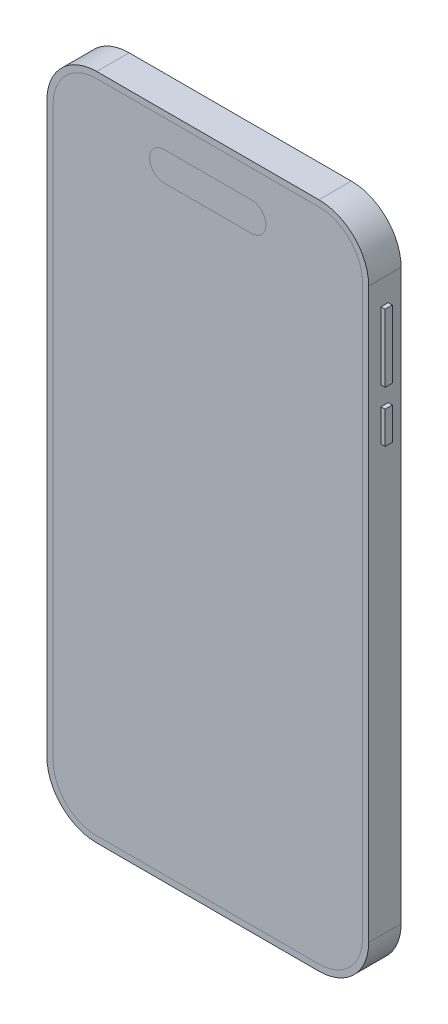
SolidWorks part; units mm, degrees
ref_plane "前视基准面" through (0, 0, 0) normal (0, 0, 1) x (1, 0, 0)
ref_plane "上视基准面" through (0, 0, 0) normal (0, 1, 0) x (1, 0, 0)
ref_plane "右视基准面" through (0, 0, 0) normal (1, 0, 0) x (0, 0, -1)
other "Configuration Table"
sketch "草图1" plane through (0, 0, 0) normal (0, 0, 1) x (1, 0, 0)
  line L1 (-26.75, -80.45) -> (26.75, -80.45)
  line L2 (-38.75, -68.45) -> (-38.75, 68.45)
  line L3 (-26.75, 80.45) -> (26.75, 80.45)
  line L4 (38.75, -68.45) -> (38.75, 68.45)
  line L5 (-38.75, -80.45) -> (38.75, 80.45) construction
  line L6 (-38.75, 80.45) -> (38.75, -80.45) construction
  arc A0 (26.75, -80.45) -> (38.75, -68.45) centre (26.75, -68.45) ccw
  arc A1 (-38.75, 68.45) -> (-26.75, 80.45) centre (-26.75, 68.45) cw
  arc A2 (-26.75, -80.45) -> (-38.75, -68.45) centre (-26.75, -68.45) cw
  arc A3 (26.75, 80.45) -> (38.75, 68.45) centre (26.75, 68.45) cw
  point P0 (0, 0)
  dimension "D3" = 12
  dimension "D1" = 77.5
  dimension "D2" = 160.9
extrude "凸台-拉伸1" add sketch "草图1" along normal blind 7.8
sketch "草图4" plane through (0, 0, 7.8) normal (0, 0, 1) x (1, 0, 0)
  line L0 (-10.5, 68.8) -> (10.5, 68.8) construction
  line L1 (-10.5, 72.3) -> (10.5, 72.3)
  line L2 (-10.5, 65.3) -> (10.5, 65.3)
  line L3 (26.75, 80.45) -> (-26.75, 80.45) construction
  arc A0 (-10.5, 72.3) -> (-10.5, 65.3) centre (-10.5, 68.8) ccw
  arc A1 (10.5, 65.3) -> (10.5, 72.3) centre (10.5, 68.8) ccw
  point P2 (0, 68.8)
  dimension "D1" = 3.5
  dimension "D2" = 21
  dimension "D3" = 8.15
split line "分割线1"
sketch "草图7" plane through (0, 0, 7.8) normal (0, 0, 1) x (1, 0, 0)
sketch "草图9" plane through (0, 0, 7.8) normal (0, 0, 1) x (1, 0, 0)
sketch "草图10" plane through (0, 0, 7.8) normal (0, 0, 1) x (1, 0, 0)
  line L2 (-37.25, 68.45) -> (-37.25, -68.45)
  line L3 (-37.25, 68.45) -> (-37.25, -68.45)
  line L5 (26.75, 78.95) -> (-26.75, 78.95)
  line L6 (26.75, 78.95) -> (-26.75, 78.95)
  line L8 (37.25, -68.45) -> (37.25, 68.45)
  line L9 (37.25, -68.45) -> (37.25, 68.45)
  line L11 (-26.75, -78.95) -> (26.75, -78.95)
  line L12 (-26.75, -78.95) -> (26.75, -78.95)
  arc A2 (-26.75, 78.95) -> (-37.25, 68.45) centre (-26.75, 68.45) ccw
  arc A3 (-26.75, 78.95) -> (-37.25, 68.45) centre (-26.75, 68.45) ccw
  arc A5 (37.25, 68.45) -> (26.75, 78.95) centre (26.75, 68.45) ccw
  arc A6 (37.25, 68.45) -> (26.75, 78.95) centre (26.75, 68.45) ccw
  arc A7 (-37.25, -68.45) -> (-26.75, -78.95) centre (-26.75, -68.45) ccw
  arc A8 (26.75, -78.95) -> (37.25, -68.45) centre (26.75, -68.45) ccw
  arc A9 (26.75, -78.95) -> (37.25, -68.45) centre (26.75, -68.45) ccw
  arc A10 (-37.25, -68.45) -> (-26.75, -78.95) centre (-26.75, -68.45) ccw
  dimension "D1" = 1.5
  dimension "D2" = 1.5
  dimension "D3" = 1.5
  dimension "D4" = 1.5
  dimension "D5" = 1.5
  dimension "D6" = 1.5
  dimension "D7" = 1.5
  dimension "D8" = 1.5
split line "分割线3"
sketch "草图15" plane through (0, 0, 0) normal (0, 0, -1) x (-1, 0, 0)
  line L0 (-38.75, -68.45) -> (-38.75, 68.45) construction
  line L1 (-27.75, 37.45) -> (-5.75, 37.45)
  line L2 (-35.75, 45.45) -> (-35.75, 67.45)
  line L3 (-27.75, 75.45) -> (-5.75, 75.45)
  line L4 (2.25, 45.45) -> (2.25, 67.45)
  line L5 (-16.75, 75.45) -> (-16.75, 37.45) construction
  line L6 (-35.75, 56.45) -> (2.25, 56.45) construction
  line L7 (-26.75, 80.45) -> (26.75, 80.45) construction
  line L8 (-24.5442, 65.45) -> (-24.5442, 47.45) construction
  line L9 (-24.5442, 47.45) -> (-8.9558, 56.45) construction
  line L10 (-8.9558, 56.45) -> (-24.5442, 65.45) construction
  line L11 (-24.5442, 56.45) -> (-8.9558, 56.45)
  circle A0 centre (-24.5442, 65.45) radius 7.5
  circle A1 centre (-8.9558, 56.45) radius 7.5
  circle A2 centre (-24.5442, 47.45) radius 7.5
  arc A3 (-5.75, 75.45) -> (2.25, 67.45) centre (-5.75, 67.45) cw
  arc A4 (2.25, 45.45) -> (-5.75, 37.45) centre (-5.75, 45.45) cw
  arc A5 (-27.75, 37.45) -> (-35.75, 45.45) centre (-27.75, 45.45) cw
  arc A6 (-35.75, 67.45) -> (-27.75, 75.45) centre (-27.75, 67.45) cw
  circle A7 centre (-8.9558, 68.45) radius 2
  point P0 (-16.75, 56.45)
  point P12 (-16.75, 56.45)
  point P17 (2.25, 75.45)
  point P20 (2.25, 37.45)
  point P26 (-35.75, 75.45)
  dimension "D6" = 15
  dimension "D7" = 8
  dimension "D8" = 4
  dimension "D1" = 38
  dimension "D2" = 38
  dimension "D3" = 3
  dimension "D4" = 5
  dimension "D5" = 18
  dimension "D9" = 12
extrude "凸台-拉伸2" add sketch "草图15" along normal blind 1.2 contours A6 L2 A5 L1 A4 L4 A3 L3 A7 A2 A1 A0 | A0 | A7 | A1 | A2 region at (33.0269, 40.1731, 0) region at (24.5442, 65.45, 0) region at (8.9558, 49.1621, 0) region at (24.5442, 47.45, 0) region at (8.9558, 68.45, 0)
extrude "凸台-拉伸3" add sketch "草图15<4>" along normal blind 4 contours A0 | A2 | A1 region at (24.5442, 65.45, 0) region at (8.9558, 49.1621, 0) region at (24.5442, 47.45, 0)
sketch "草图15<4>" plane through (0, 0, 0) normal (0, 0, -1) x (-1, 0, 0) same geometry as "草图15"
extrude "凸台-拉伸5" add sketch "草图15<6>" along normal blind 2 contours A7 region at (8.9558, 68.45, 0)
sketch "草图15<6>" plane through (0, 0, 0) normal (0, 0, -1) x (-1, 0, 0) same geometry as "草图15"
sketch "草图18" plane through (0, 0, -4) normal (0, 0, -1) x (-1, 0, 0)
  line L4 (-26.75, -80.45) -> (26.75, -80.45)
  line L5 (38.75, -68.45) -> (38.75, 68.45)
  line L6 (26.75, 80.45) -> (-26.75, 80.45)
  line L7 (-38.75, 68.45) -> (-38.75, -68.45)
  line L8 (-26.75, -80.45) -> (26.75, -80.45)
  line L9 (38.75, -68.45) -> (38.75, 68.45)
  line L10 (26.75, 80.45) -> (-26.75, 80.45)
  line L11 (-38.75, 68.45) -> (-38.75, -68.45)
  circle A0 centre (-24.5442, 47.45) radius 7.5 construction
  circle A1 centre (-24.5442, 65.45) radius 7.5 construction
  circle A2 centre (-8.9558, 56.45) radius 7.5 construction
  circle A3 centre (-24.5442, 47.45) radius 7.5
  arc A4 (-38.75, -68.45) -> (-26.75, -80.45) centre (-26.75, -68.45) ccw
  arc A5 (26.75, -80.45) -> (38.75, -68.45) centre (26.75, -68.45) ccw
  arc A6 (38.75, 68.45) -> (26.75, 80.45) centre (26.75, 68.45) ccw
  arc A7 (-26.75, 80.45) -> (-38.75, 68.45) centre (-26.75, 68.45) ccw
  arc A8 (-38.75, -68.45) -> (-26.75, -80.45) centre (-26.75, -68.45) ccw
  arc A9 (26.75, -80.45) -> (38.75, -68.45) centre (26.75, -68.45) ccw
  arc A10 (38.75, 68.45) -> (26.75, 80.45) centre (26.75, 68.45) ccw
  arc A11 (-26.75, 80.45) -> (-38.75, 68.45) centre (-26.75, 68.45) ccw
  circle A12 centre (-24.5442, 65.45) radius 7.5
  circle A13 centre (-8.9558, 56.45) radius 7.5
  circle A14 centre (-24.5442, 47.45) radius 7.5
  circle A15 centre (-8.9558, 56.45) radius 7.5
  circle A16 centre (-24.5442, 65.45) radius 7.5
  circle A17 centre (-24.5442, 65.45) radius 6.5
  circle A18 centre (-8.9558, 56.45) radius 6.5
  circle A19 centre (-24.5442, 47.45) radius 6.5
  dimension "D1" = 0
  dimension "D2" = 1
split line "分割线4"
sketch "草图19" plane through (38.75, 0, 0) normal (1, 0, 0) x (0, 0, -1)
  line L1 (-4.8402, 62.6491) -> (-3.1078, 62.6491)
  line L2 (-4.8402, 62.6491) -> (-4.8402, 46.3442)
  line L3 (-4.8402, 46.3442) -> (-3.1078, 46.3442)
  line L4 (-3.1078, 62.6491) -> (-3.1078, 46.3442)
  line L5 (-3.974, 46.3442) -> (-3.974, 62.6491) construction
  line L6 (-4.8402, 54.4967) -> (-3.1078, 54.4967) construction
  line L9 (-4.8402, 34.0145) -> (-3.1078, 34.0145)
  line L10 (-4.8402, 34.0145) -> (-4.8402, 41.796)
  line L11 (-4.8402, 41.796) -> (-3.1078, 41.796)
  line L12 (-3.1078, 34.0145) -> (-3.1078, 41.796)
  line L13 (-3.974, 41.796) -> (-3.974, 34.0145) construction
  line L14 (-4.8402, 37.9052) -> (-3.1078, 37.9052) construction
  point P0 (-3.974, 54.4967)
  point P4 (-3.974, 37.9052)
extrude "凸台-拉伸6" add sketch "草图19" along normal blind 1
sketch "草图20" plane through (38.75, 0, 0) normal (1, 0, 0) x (0, 0, -1)
  line L1 (-6.8288, -25.8015) -> (-1.6959, -25.8015)
  line L2 (-6.8288, -25.8015) -> (-6.8288, -9.1198)
  line L3 (-6.8288, -9.1198) -> (-1.6959, -9.1198)
  line L4 (-1.6959, -25.8015) -> (-1.6959, -9.1198)
  line L5 (-4.2623, -9.1198) -> (-4.2623, -25.8015) construction
  line L6 (-6.8288, -17.4606) -> (-1.6959, -17.4606) construction
  point P0 (-4.2623, -17.4606)
extrude "凸台-拉伸8" add sketch "草图20" against normal blind 1
